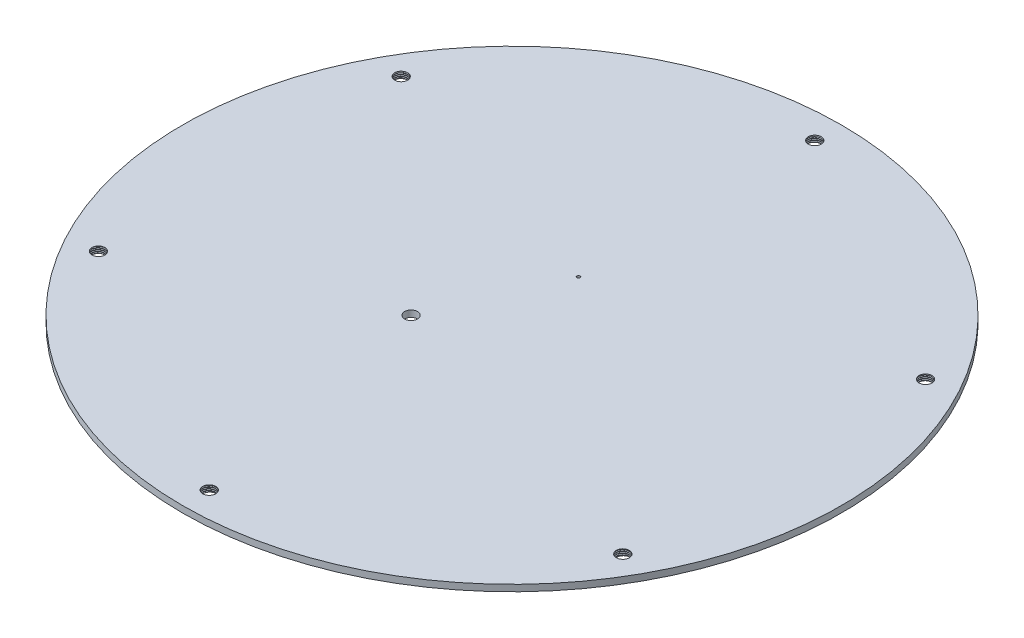
SolidWorks part; units mm, degrees
material "1060 Alloy"
ref_plane "Front Plane" through (0, 0, 0) normal (0, 0, 1) x (1, 0, 0)
ref_plane "Top Plane" through (0, 0, 0) normal (0, 1, 0) x (1, 0, 0)
ref_plane "Right Plane" through (0, 0, 0) normal (1, 0, 0) x (0, 0, -1)
sketch "Sketch1" plane through (0, 0, 0) normal (0, 1, 0) x (1, 0, 0)
  circle A0 centre (0, 0) radius 50.8
  circle A1 centre (0, 46.67) radius 1
  circle A2 centre (40.4174, 23.335) radius 1
  circle A3 centre (40.4174, -23.335) radius 1
  circle A4 centre (0, -46.67) radius 1
  circle A5 centre (-40.4174, -23.335) radius 1
  circle A6 centre (-40.4174, 23.335) radius 1
  point P17 (0, 0)
  dimension "D1" = 101.6
  dimension "D2" = 2
  dimension "D3" = 46.67
  dimension "D4" = 6
extrude "Boss-Extrude1" add sketch "Sketch1" along normal blind 1
thread "Thread1" pitch 0.25 method cut profile "Thread Profile1" start angle 0, offset 0, length 10, pitch 0.25, diameter 2
ref_plane "Plane1" through (-41.4174, 1, 23.335) normal (0, 0, 1) x (-1, 0, 0)
sketch "Thread Profile1" plane through (-41.4174, 1, 23.335) normal (0, 0, 1) x (-1, 0, 0)
  line L0 (0, 0) -> (0, 0.25) construction
  line L1 (0, 0) -> (0.1353, 0.0781)
  line L2 (0.1353, 0.0781) -> (0.1353, 0.1094)
  line L3 (0.1353, 0.1094) -> (0, 0.1875)
  line L4 (0.1353, 0.0937) -> (0, 0.0937) construction
  line L11 (0, 0) -> (0, 0.1875)
  point P2 (0, 0)
  dimension "Pitch" = 0.25
  dimension "Profile_Angle" = 60
  dimension "Profile_Land" = 0.0312
  dimension "Profile_Height" = 0.1353
pattern_circular "CirPattern1" count 6 over 360 about axis through (0, 0, 0) along (0, 1, 0) of "Thread1"
sketch "Sketch2" plane through (0, 1, 0) normal (0, 1, 0) x (1, 0, 0)
  line L0 (0, 0) -> (0, 10.25) construction
  line L1 (0, 10.25) -> (0, 0) construction
  line L2 (0, 0) -> (-20.5223, -20.5223) construction
  circle A0 centre (0, 10.25) radius 0.25
  circle A1 centre (-7.7782, -7.7782) radius 1
  dimension "D1" = 0.5
  dimension "D3" = 2
  dimension "D2" = 10.25
  dimension "D4" = 11
extrude "Cut-Extrude1" cut sketch "Sketch2" against normal through all both and the other way through all
